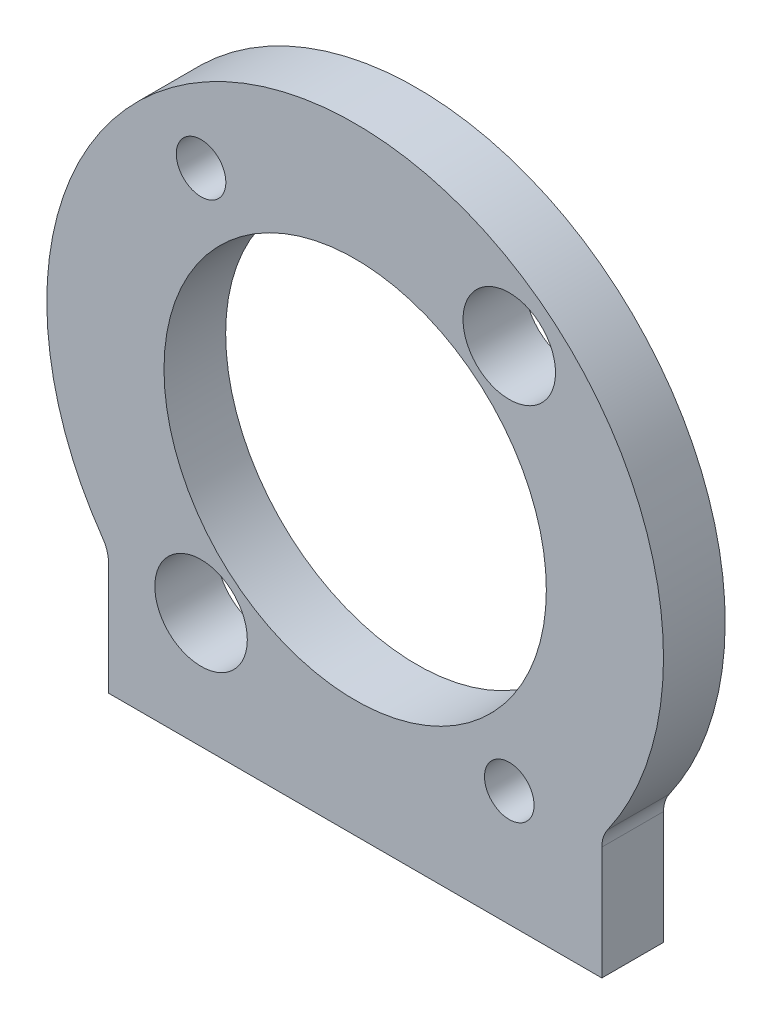
SolidWorks part; units mm, degrees
material "6061 Alloy"
ref_plane "Front" through (0, 0, 0) normal (0, 0, 1) x (1, 0, 0)
ref_plane "Top" through (0, 0, 0) normal (0, 1, 0) x (1, 0, 0)
ref_plane "Right" through (0, 0, 0) normal (1, 0, 0) x (0, 0, -1)
sketch "Sketch1" plane through (0, 0, 0) normal (0, 0, 1) x (1, 0, 0)
  line L0 (-50.8, 63.5) -> (0, 0) construction
  line L1 (0, 0) -> (-50.8, 0)
  line L2 (0, 0) -> (0, 11.6695)
  line L3 (0, 63.5) -> (-50.8, 63.5) construction
  line L4 (-50.8, 0) -> (-50.8, 11.6695)
  line L5 (0, 63.5) -> (-50.8, 0) construction
  line L6 (0, 50.8) -> (0, 63.5) construction
  line L7 (-50.8, 50.8) -> (-50.8, 63.5) construction
  circle A0 centre (-25.4, 31.75) radius 19.685
  circle A2 centre (-25.4, 31.75) radius 25.4 construction
  circle A4 centre (-41.2673, 51.5841) radius 2.5527
  circle A5 centre (-9.5327, 51.5841) radius 4.7625
  circle A6 centre (-9.5327, 11.9159) radius 2.5527
  circle A7 centre (-41.2673, 11.9159) radius 4.7625
  arc A9 (0.5773, 13.495) -> (-51.3773, 13.495) centre (-25.4, 31.75) ccw
  arc A10 (0, 11.6695) -> (0.5773, 13.495) centre (3.175, 11.6695) cw
  arc A11 (-50.8, 11.6695) -> (-51.3773, 13.495) centre (-53.975, 11.6695) ccw
  dimension "D2" = 39.37
  dimension "D4" = 50.8
  dimension "D5" = 5.1054
  dimension "D6" = 9.525
  dimension "D7" = 31.75
  dimension "D8" = 3.175
  dimension "D1" = 50.8
  dimension "D3" = 31.75
extrude "Boss-Extrude1" add sketch "Sketch1" along normal blind 6.35
